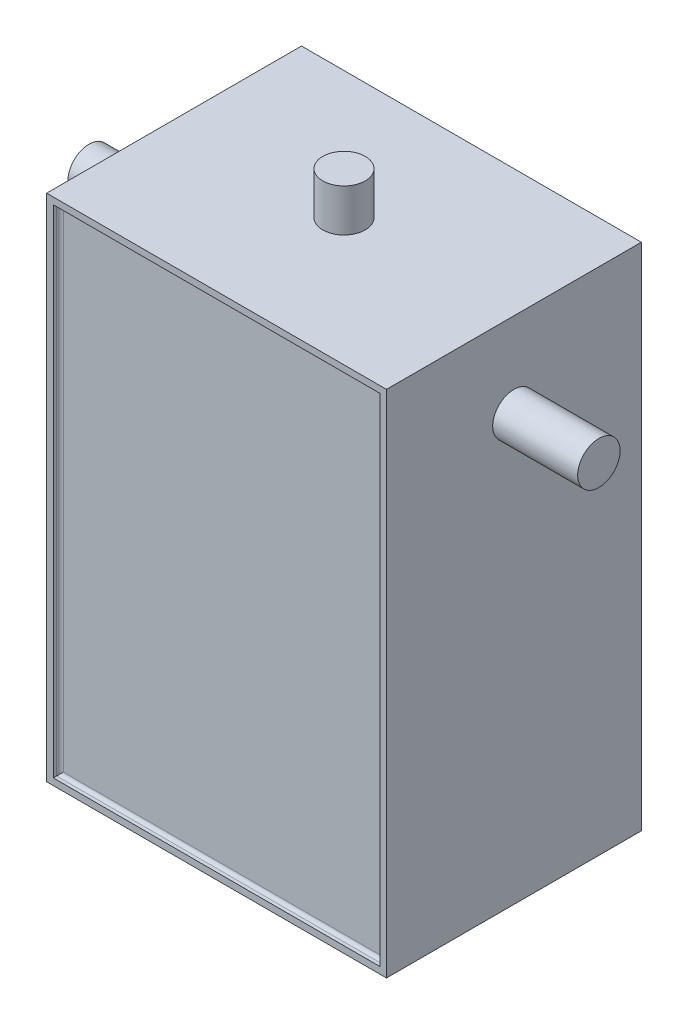
SolidWorks part; units mm, degrees
ref_plane "Front Plane" through (0, 0, 0) normal (0, 0, 1) x (1, 0, 0)
ref_plane "Top Plane" through (0, 0, 0) normal (0, 1, 0) x (1, 0, 0)
ref_plane "Right Plane" through (0, 0, 0) normal (1, 0, 0) x (0, 0, -1)
sketch "Sketch1" plane through (0, 0, 0) normal (0, 0, 1) x (1, 0, 0)
  line L1 (0, 0) -> (101.6, 0)
  line L2 (0, 0) -> (0, 152.4)
  line L3 (0, 152.4) -> (101.6, 152.4)
  line L4 (101.6, 0) -> (101.6, 152.4)
  dimension "D1" = 152.4
  dimension "D2" = 101.6
extrude "Boss-Extrude1" add sketch "Sketch1" against normal blind 76.2
sketch "Sketch2" plane through (101.6, 0, 0) normal (1, 0, 0) x (0, 0, -1)
  line L0 (76.2, 152.4) -> (0, 152.4) construction
  circle A0 centre (38.1, 127) radius 6.35
  dimension "D2" = 12.7
  dimension "D1" = 25.4
extrude "Boss-Extrude2" add sketch "Sketch2" along normal blind 25.4
pattern_linear "LPattern1" count 2 spacing 127 along (-1, 0, 0) of "Boss-Extrude2"
sketch "Sketch3" plane through (0, 0, 0) normal (0, -1, 0) x (1, 0, 0)
  line L0 (0, -76.2) -> (0, 0) construction
  circle A0 centre (50.8, -38.1) radius 12.7
  point P4 (0, -38.1)
  dimension "D2" = 25.4
  dimension "D1" = 0
extrude "Boss-Extrude3" add sketch "Sketch3" along normal blind 12.7
sketch "Sketch4" plane through (0, 0, 0) normal (0, 0, 1) x (1, 0, 0)
  line L8 (2, 150.4) -> (2, 2)
  line L9 (2, 2) -> (99.6, 2)
  line L10 (99.6, 2) -> (99.6, 150.4)
  line L11 (99.6, 150.4) -> (2, 150.4)
  line L12 (2, 150.4) -> (2, 2)
  line L13 (2, 2) -> (99.6, 2)
  line L14 (99.6, 2) -> (99.6, 150.4)
  line L15 (99.6, 150.4) -> (2, 150.4)
  dimension "D1" = 2
extrude "Cut-Extrude1" cut sketch "Sketch4" against normal blind 2
fillet "Fillet1" radius 1 4 edges at (50.8, 2, -2) (2, 76.2, -2) (99.6, 76.2, -2) (50.8, 150.4, -2)
ref_plane "Plane1" through (0, 0, -38.1) normal (0, 0, 1) x (1, 0, 0)
mirror "Mirror1" about plane through (0, 0, -38.1) normal (0, 0, 1) of "Fillet1", "Cut-Extrude1"
sketch "Sketch5" plane through (0, 152.4, 0) normal (0, 1, 0) x (1, 0, 0)
  line L0 (50.8, 76.2) -> (50.8, 0)
  line L6 (0, 0) -> (101.6, 0)
  line L7 (101.6, 0) -> (101.6, 76.2)
  line L8 (101.6, 76.2) -> (0, 76.2)
  line L9 (0, 76.2) -> (0, 0)
  line L10 (0, 0) -> (101.6, 0)
  line L11 (101.6, 0) -> (101.6, 76.2)
  line L12 (101.6, 76.2) -> (0, 76.2)
  line L13 (0, 76.2) -> (0, 0)
  circle A0 centre (50.8, 38.1) radius 6.35
  dimension "D2" = 12.7
  dimension "D1" = 0
extrude "Boss-Extrude4" add sketch "Sketch5" along normal blind 12.7 contours L0 A0 | L0 A0 region at (53.495, 152.4, -38.1) region at (48.105, 152.4, -38.1)
